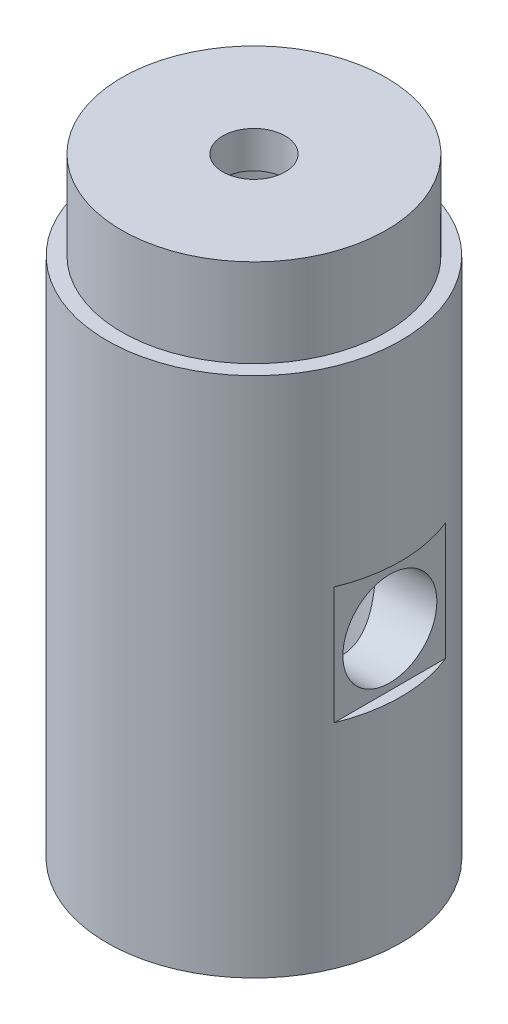
SolidWorks part; units mm, degrees
material "6061-T6 (SS)"
ref_plane "Piano frontale" through (0, 0, 0) normal (0, 0, 1) x (1, 0, 0)
ref_plane "Piano superiore" through (0, 0, 0) normal (0, 1, 0) x (1, 0, 0)
ref_plane "Piano destro" through (0, 0, 0) normal (1, 0, 0) x (0, 0, -1)
sketch "Schizzo1" plane through (0, 0, 0) normal (0, 0, 1) x (1, 0, 0)
  line L0 (0, 0) -> (0, 31.0712) construction
  line L1 (-12, 0) -> (-20, 0)
  line L2 (-20, 0) -> (-20, 71)
  line L3 (-20, 71) -> (-18, 71)
  line L4 (-18, 71) -> (-18, 83)
  line L5 (-18, 83) -> (-4.25, 83)
  line L6 (-4.25, 83) -> (-4.25, 78)
  line L7 (-4.25, 78) -> (-12, 78)
  line L8 (-12, 78) -> (-12, 0)
  dimension "D1" = 24
  dimension "D2" = 40
  dimension "D3" = 36
  dimension "D4" = 5
  dimension "D5" = 78
  dimension "D6" = 12
  dimension "D7" = 8.5
revolve "Rivoluzione1" add sketch "Schizzo1" angle 360 about L0
sketch "Schizzo2" plane through (0, 0, 0) normal (1, 0, 0) x (0, 0, -1)
  line L1 (8, 45) -> (-8, 45)
  line L2 (8, 45) -> (8, 29)
  line L3 (8, 29) -> (-8, 29)
  line L4 (-8, 45) -> (-8, 29)
  line L5 (8, 45) -> (-8, 29) construction
  line L6 (8, 29) -> (-8, 45) construction
  point P0 (0, 37)
  dimension "D1" = 16
  dimension "D2" = 37
extrude "Taglio-Estrusione1" cut sketch "Schizzo2" against normal blind 1.5 from offset 20
hole_wizard "Foro Ø12.8 (12.8)-1" positions "Schizzo3" profile "Schizzo4" hole size "Ø12.8" standard "ISO"
sketch "Schizzo3" plane through (18.5, 0, 0) normal (1, 0, 0) x (0, 0, -1)
  point P0 (0, 36.3049)
sketch "Schizzo4" plane through (18.5, 36.3049, 0) normal (0, 1, 0) x (0, 0, -1)
  line L0 (0, 0) -> (0, 19)
  line L1 (0, 19) -> (6.4, 15.1545)
  line L2 (6.4, 15.1545) -> (6.4, 0)
  line L5 (6.4, 0) -> (0, 0)
  line L10 (0, 19) -> (-6.4, 15.1545) construction
  line L11 (0, -6.35) -> (0, 107.95) construction
  dimension "Hole Dia." = 12.8
  dimension "Hole Depth" = 19
  dimension "Drill Angle" = 118
mirror "Specchia1" about plane through (0, 0, 0) normal (1, 0, 0) of "Foro Ø12.8 (12.8)-1", "Taglio-Estrusione1"
